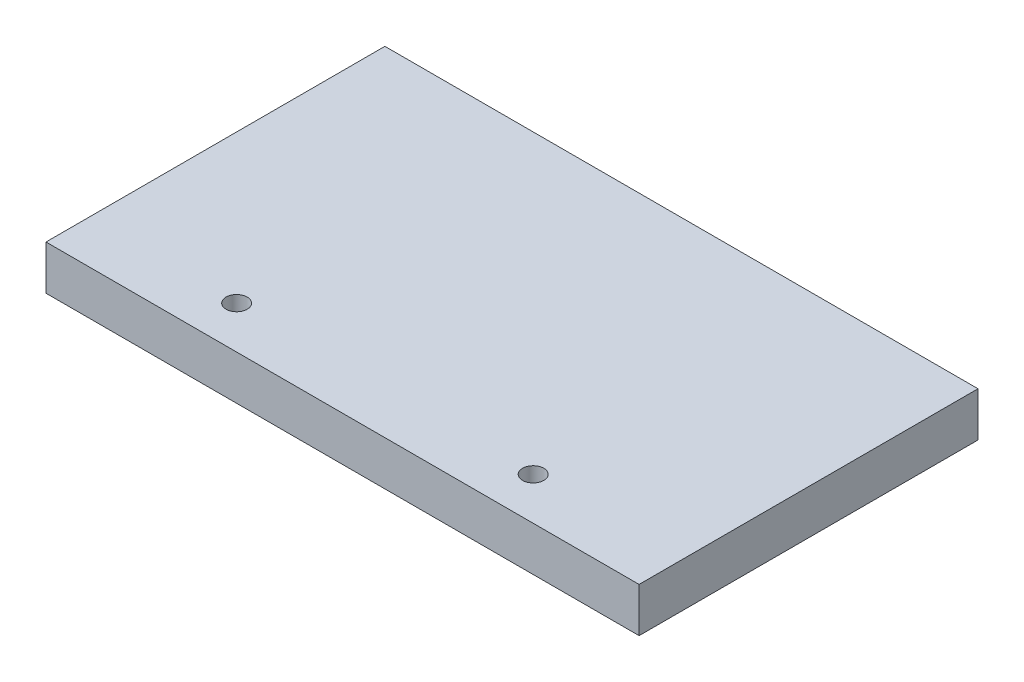
SolidWorks part; units mm, degrees
ref_plane "Front Plane" through (0, 0, 0) normal (0, 0, 1) x (1, 0, 0)
ref_plane "Top Plane" through (0, 0, 0) normal (0, 1, 0) x (1, 0, 0)
ref_plane "Right Plane" through (0, 0, 0) normal (1, 0, 0) x (0, 0, -1)
sketch "Sketch1" plane through (0, 0, 0) normal (0, 1, 0) x (1, 0, 0)
  line L1 (0, 0) -> (88.9, 0)
  line L2 (0, 0) -> (0, 50.8)
  line L3 (0, 50.8) -> (88.9, 50.8)
  line L4 (88.9, 0) -> (88.9, 50.8)
  dimension "D1" = 88.9
  dimension "D2" = 50.8
extrude "Boss-Extrude1" add sketch "Sketch1" along normal blind 6.6548
sketch "Sketch2" plane through (0, 6.6548, 0) normal (0, 1, 0) x (1, 0, 0)
  line L0 (22.225, 6.35) -> (66.675, 6.35) construction
  line L1 (44.45, 6.35) -> (44.45, 0) construction
  line L2 (0, 0) -> (88.9, 0) construction
  line L3 (44.45, 6.35) -> (44.45, 50.8) construction
  line L4 (88.9, 50.8) -> (0, 50.8) construction
  line L6 (66.675, 6.35) -> (88.9, 6.35) construction
  line L7 (88.9, 0) -> (88.9, 50.8) construction
  circle A0 centre (22.225, 6.35) radius 1.5875
  circle A1 centre (66.675, 6.35) radius 1.5875
  dimension "D2" = 3.175
  dimension "D1" = 44.45
  dimension "D3" = 6.35
extrude "Cut-Extrude1" cut sketch "Sketch2" against normal through all
